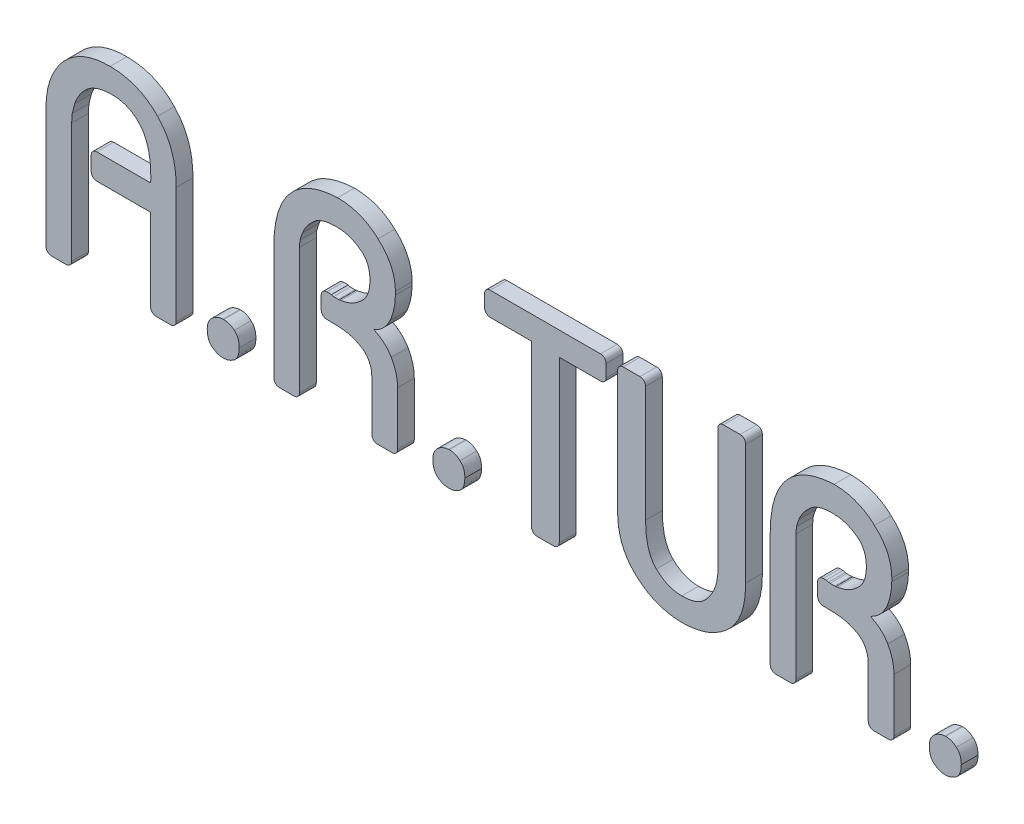
SolidWorks part; units mm, degrees
ref_plane "Plan de face" through (0, 0, 0) normal (0, 0, 1) x (1, 0, 0)
ref_plane "Plan de dessus" through (0, 0, 0) normal (0, 1, 0) x (1, 0, 0)
ref_plane "Plan de droite" through (0, 0, 0) normal (1, 0, 0) x (0, 0, -1)
sketch "Esquisse2" plane through (0, 0, 0) normal (0, 0, 1) x (1, 0, 0)
  line L3 (0, 0) -> (0, 50.5726) construction
  line L4 (0, 0) -> (128.9274, 0) construction
  line L5 (-85, -17.6) -> (130.6748, -17.6) construction
  line L6 (-85, -17.6) -> (-85, 56.622) construction
  line L7 (85, -17.6) -> (85, 56.622) construction
  line L8 (-85, 17.6) -> (130.6748, 17.6) construction
  text T0 "A.R.TUR." font "Bauhaus" height in points 135
extrude "Boss.-Extru.1" add sketch "Esquisse2" along normal blind 3
sketch "Esquisse3" plane through (-76.9878, 0, 0) normal (-1, 0, 0) x (0, 0, 1)
  line L4 (0, 2.6554) -> (0, -1.9059)
  line L5 (0, -1.9059) -> (3, -1.9059)
  line L6 (3, -1.9059) -> (3, 2.6554)
  line L7 (3, 2.6554) -> (0, 2.6554)
  line L8 (0, 2.6554) -> (0, -1.9059)
  line L9 (0, -1.9059) -> (3, -1.9059)
  line L10 (3, -1.9059) -> (3, 2.6554)
  line L11 (3, 2.6554) -> (0, 2.6554)
  dimension "D1" = 0
extrude "Enlèv. mat.-Extru.1" cut sketch "Esquisse3" against normal blind 2
sketch "Esquisse4" plane through (-35.7249, 0, 0) normal (-1, 0, 0) x (0, 0, 1)
  line L4 (0, 1.5379) -> (0, -2.6861)
  line L5 (0, -2.6861) -> (3, -2.6861)
  line L6 (3, -2.6861) -> (3, 1.5379)
  line L7 (3, 1.5379) -> (0, 1.5379)
  line L8 (0, 1.5379) -> (0, -2.6861)
  line L9 (0, -2.6861) -> (3, -2.6861)
  line L10 (3, -2.6861) -> (3, 1.5379)
  line L11 (3, 1.5379) -> (0, 1.5379)
  dimension "D1" = 0
extrude "Enlèv. mat.-Extru.2" cut sketch "Esquisse4" against normal blind 2
sketch "Esquisse5" plane through (53.3371, 0, 0) normal (-1, 0, 0) x (0, 0, 1)
  line L4 (0, 1.5379) -> (0, -2.6861)
  line L5 (0, -2.6861) -> (3, -2.6861)
  line L6 (3, -2.6861) -> (3, 1.5379)
  line L7 (3, 1.5379) -> (0, 1.5379)
  line L8 (0, 1.5379) -> (0, -2.6861)
  line L9 (0, -2.6861) -> (3, -2.6861)
  line L10 (3, -2.6861) -> (3, 1.5379)
  line L11 (3, 1.5379) -> (0, 1.5379)
  dimension "D1" = 0
extrude "Enlèv. mat.-Extru.3" cut sketch "Esquisse5" against normal blind 2
sketch "Esquisse6" plane through (0, -2.6861, 0) normal (0, 1, 0) x (1, 0, 0)
  line L4 (53.3371, 0) -> (53.3371, -3)
  line L5 (53.3371, -3) -> (55.3371, -3)
  line L6 (55.3371, -3) -> (55.3371, 0)
  line L7 (55.3371, 0) -> (53.3371, 0)
  line L8 (53.3371, 0) -> (53.3371, -3)
  line L9 (53.3371, -3) -> (55.3371, -3)
  line L10 (55.3371, -3) -> (55.3371, 0)
  line L11 (55.3371, 0) -> (53.3371, 0)
  dimension "D1" = 0
extrude "Enlèv. mat.-Extru.4" cut sketch "Esquisse6" against normal up to next
sketch "Esquisse7" plane through (0, -2.6861, 0) normal (0, 1, 0) x (1, 0, 0)
  line L4 (-35.7249, 0) -> (-35.7249, -3)
  line L5 (-35.7249, -3) -> (-33.7249, -3)
  line L6 (-33.7249, -3) -> (-33.7249, 0)
  line L7 (-33.7249, 0) -> (-35.7249, 0)
  line L8 (-35.7249, 0) -> (-35.7249, -3)
  line L9 (-35.7249, -3) -> (-33.7249, -3)
  line L10 (-33.7249, -3) -> (-33.7249, 0)
  line L11 (-33.7249, 0) -> (-35.7249, 0)
  dimension "D1" = 0
extrude "Enlèv. mat.-Extru.5" cut sketch "Esquisse7" against normal up to next
fillet "Congé1" radius 1 5 edges at (-59.7405, -17.6, 1.5) (-64.351, -17.6, 1.5) (-83.1024, -17.6, 1.5) (-74.9878, -1.9059, 1.5) (-74.9878, 2.6554, 1.5)
fillet "Congé2" radius 1 6 edges at (-20.0308, -17.6, 1.5) (-24.6484, -17.6, 1.5) (-33.7249, 1.5379, 1.5) (-33.7249, -2.7287, 1.5) (-37.6155, -17.6, 1.5) (-42.2331, -17.6, 1.5)
fillet "Congé3" radius 1 4 edges at (42.4292, 16.4519, 1.5) (37.4251, 16.4519, 1.5) (19.4539, 16.4519, 1.5) (24.458, 16.4519, 1.5)
fillet "Congé4" radius 1 7 edges at (57.1745, 1.5379, 1.5) (55.3371, 1.5379, 1.5) (55.3371, -2.7287, 1.5) (69.0311, -17.6, 1.5) (64.4136, -17.6, 1.5) (51.4465, -17.6, 1.5) (46.8289, -17.6, 1.5)
fillet "Congé6" radius 1 6 edges at (17.3876, 16.4519, 1.5) (17.3876, 12.2279, 1.5) (-4.4211, 16.4519, 1.5) (-4.4211, 12.2279, 1.5) (3.9777, -17.6, 1.5) (8.9818, -17.6, 1.5)
fillet "Congé7" radius 1 1 edges at (-78.4918, -17.6, 1.5)
